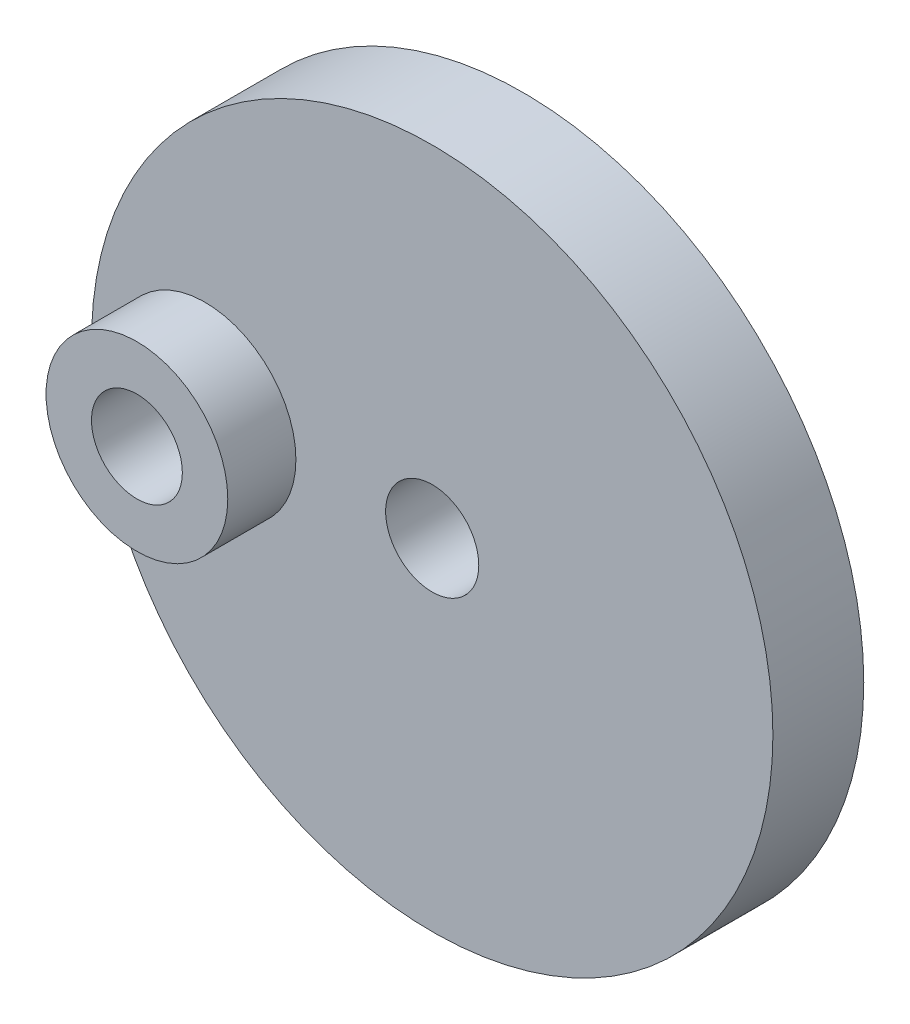
SolidWorks part; units mm, degrees
ref_plane "前视基准面" through (0, 0, 0) normal (0, 0, 1) x (1, 0, 0)
ref_plane "上视基准面" through (0, 0, 0) normal (0, 1, 0) x (1, 0, 0)
ref_plane "右视基准面" through (0, 0, 0) normal (1, 0, 0) x (0, 0, -1)
other "Configuration Table"
sketch "草图1" plane through (0, 0, 0) normal (0, 0, 1) x (1, 0, 0)
  line L0 (-20, 0) -> (0, 0) construction
  circle A0 centre (0, 0) radius 30
  circle A1 centre (0, 0) radius 4.1
  circle A2 centre (-20, 0) radius 8
  circle A3 centre (-20, 0) radius 4
  dimension "D1" = 60
  dimension "D2" = 8.2
  dimension "D4" = 16
  dimension "D5" = 8
  dimension "D3" = 20
extrude "凸台-拉伸3" add sketch "草图1" along normal blind 8 contours A0 A2 A1 region at (-29.1515, 0, 0)
extrude "凸台-拉伸4" add sketch "草图1<5>" along normal offset from surface (14 mm away) 6 separate body contours A3 A2 region at (-27.7737, 0, 0) up to face at (4.1, 0, 8) offset beyond the face yes
sketch "草图1<5>" plane through (0, 0, 0) normal (0, 0, 1) x (1, 0, 0) same geometry as "草图1"
